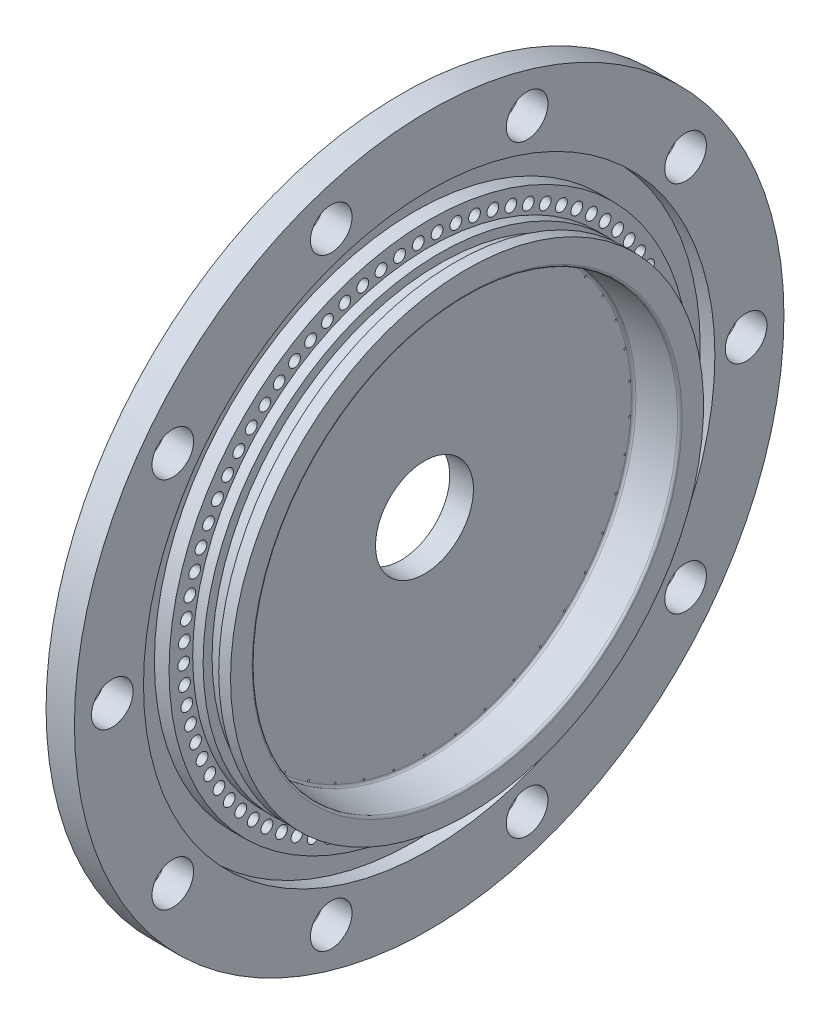
SolidWorks part; units mm, degrees
ref_plane "Front Plane" through (0, 0, 0) normal (0, 0, 1) x (1, 0, 0)
ref_plane "Top Plane" through (0, 0, 0) normal (0, 1, 0) x (1, 0, 0)
ref_plane "Right Plane" through (0, 0, 0) normal (1, 0, 0) x (0, 0, -1)
sketch "Sketch4" plane through (0, 0, 0) normal (0, 0, 1) x (1, 0, 0)
  line L0 (0, 0) -> (0, 42.055) construction
  line L1 (2.1534, 50) -> (36.2156, 50) construction
  line L2 (0, 10.35) -> (0, 75)
  line L3 (0, 75) -> (6, 75)
  line L4 (6, 75) -> (6, 60.4)
  line L5 (6, 50) -> (8.2, 50)
  line L6 (14, 50) -> (14, 45.4582)
  line L7 (13.5436, 44.9601) -> (5.4564, 44.2525)
  line L8 (0, 10.35) -> (5, 10.35)
  line L9 (5, 10.35) -> (5, 43.7544)
  line L10 (11.5, 50) -> (11.5, 48.1)
  line L11 (11.5, 48.1) -> (8.2, 48.1)
  line L12 (8.2, 48.1) -> (8.2, 50)
  line L13 (6, 55) -> (2.9, 55)
  line L14 (2.9, 55) -> (2.9, 60.4)
  line L15 (2.9, 60.4) -> (6, 60.4)
  line L16 (11.5, 50) -> (14, 50)
  line L17 (6, 55) -> (6, 50)
  line L18 (0, 0) -> (17.439, 0) construction
  arc A0 (14, 45.4582) -> (13.5436, 44.9601) centre (13.5, 45.4582) cw
  arc A1 (5.4564, 44.2525) -> (5, 43.7544) centre (5.5, 43.7544) ccw
  point P24 (14, 45)
  point P27 (5, 44.2126)
  dimension "D16" = 0.5
  dimension "D17" = 0.5
  dimension "D1" = 50
  dimension "D2" = 75
  dimension "D3" = 6
  dimension "D4" = 9
  dimension "D5" = 10.35
  dimension "D6" = 5
  dimension "D7" = 95
  dimension "D8" = 1.9
  dimension "D9" = 3.3
  dimension "D10" = 5
  dimension "D11" = 33.8626
  dimension "D12" = 3.1
  dimension "D13" = 5.4
  dimension "D14" = 55
  dimension "D15" = 2.5
revolve "Revolve2" add sketch "Sketch4" angle 360 about L18
sketch "Sketch5" plane through (6, 0, 0) normal (1, 0, 0) x (0, 0, -1)
  line L0 (0, 0) -> (0, 55.5529) construction
  line L1 (0, 0) -> (0, 51.9) construction
  line L2 (0, 0) -> (1.8113, 51.8684) construction
  line L3 (0, 0) -> (2.5152, 68.5935) construction
  circle A0 centre (0, 0) radius 51.9
  circle A1 centre (0, 51.9) radius 1.25 construction
  circle A2 centre (1.8113, 51.8684) radius 1.25 construction
  circle A3 centre (1.6755, 51.8729) radius 1.25
  point P6 (1.9018, 51.8651)
  point P16 (0, 0)
  dimension "D1" = 2
  dimension "D2" = 2
  dimension "D6" = 51.9
  dimension "D3" = 2
  dimension "D5" = 2.1
  dimension "D4" = 2
extrude "Cut-Extrude1" cut sketch "Sketch5" against normal through all and the other way through all contours A3
pattern_circular "CirPattern1" count 82 over 360 about axis through (14, 0, 0) along (-1, 0, 0) of "Cut-Extrude1"
sketch "Sketch6" plane through (6, 0, 0) normal (1, 0, 0) x (0, 0, -1)
  line L0 (0, 0) -> (67, 0) construction
  line L1 (0, 0) -> (0, 67) construction
  circle A1 centre (0, 0) radius 67 construction
  circle A2 centre (67, 0) radius 4.4
  point P11 (0, 0)
  dimension "D1" = 90
  dimension "D2" = 67
extrude "Cut-Extrude2" cut sketch "Sketch6" against normal through all contours A1 A2 | A1 A2 region at (6, 0, -67)
pattern_circular "CirPattern2" count 10 over 360 about axis through (6, 0, 0) along (-1, 0, 0) of "Cut-Extrude2"
sketch "Sketch9" plane through (5, 0, 0) normal (1, 0, 0) x (0, 0, -1)
  line L0 (0, 0) -> (0, 43.5)
  circle A0 centre (0, 43.5) radius 0.2
extrude "Cut-Extrude3" cut sketch "Sketch9" against normal up to next contours A0 region at (5, 43.3626, -0.1374)
sketch "Sketch10" plane through (0, 0, 0) normal (-1, 0, 0) x (0, 0, 1)
  circle A0 centre (0, 43.5) radius 0.7
extrude "Cut-Extrude4" cut sketch "Sketch10" against normal blind 3.8
pattern_circular "CirPattern3" count 42 over 360 about axis through (0, 0, 0) along (-1, 0, 0) of "Cut-Extrude3", "Cut-Extrude4"
